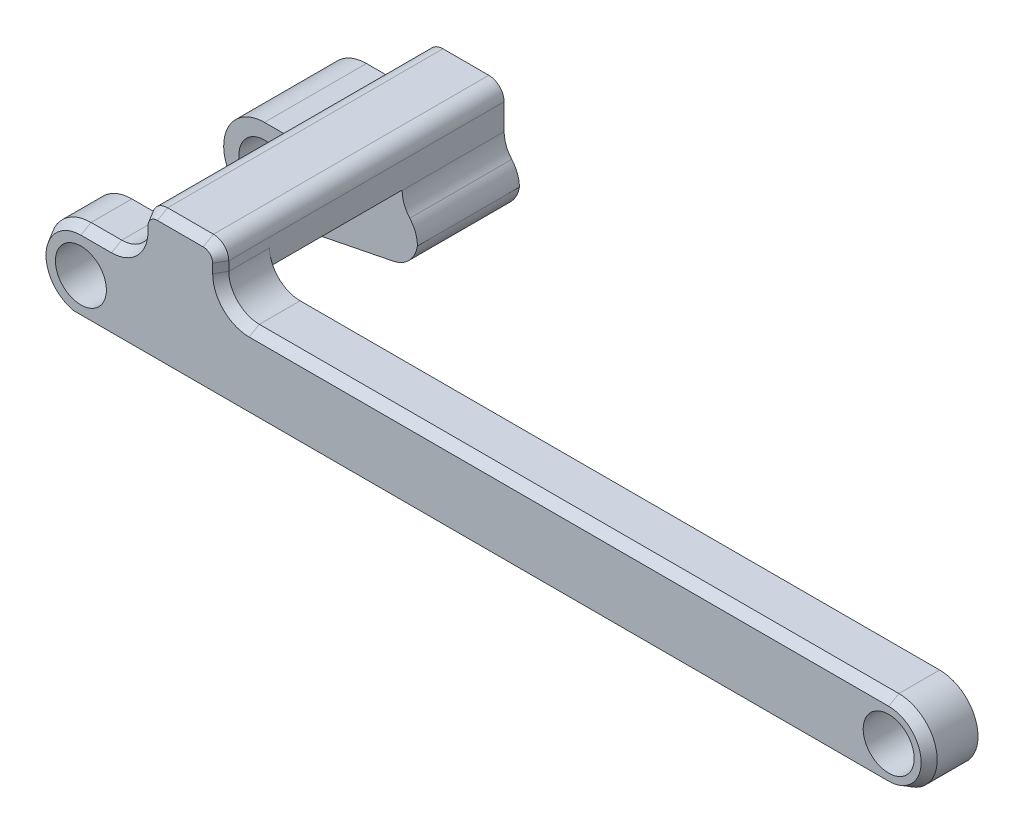
SolidWorks part; units mm, degrees
ref_plane "Front Plane" through (0, 0, 0) normal (0, 0, 1) x (1, 0, 0)
ref_plane "Top Plane" through (0, 0, 0) normal (0, 1, 0) x (1, 0, 0)
ref_plane "Right Plane" through (0, 0, 0) normal (1, 0, 0) x (0, 0, -1)
sketch "Sketch1" plane through (0, 0, 0) normal (0, 0, 1) x (1, 0, 0)
  line L0 (0, 0) -> (4.5, 0) construction
  line L1 (0, 4) -> (15, 4)
  line L2 (0, -4) -> (15, -4)
  line L3 (15, -4) -> (15, 4)
  circle A0 centre (0, 0) radius 2.5
  arc A1 (0, 4) -> (0, -4) centre (0, 0) ccw
extrude "Boss-Extrude1" add sketch "Sketch1" along normal blind 10
fillet "Fillet1" radius 3 2 edges at (15, -4, 5) (15, 4, 5)
sketch "Sketch2" plane through (0, 0, 10) normal (0, 0, 1) x (1, 0, 0)
  line L0 (15, -1) -> (0, -4)
  line L1 (0, -4) -> (12, -4) construction
  line L2 (0, -4) -> (15, -4)
  line L3 (15, -4) -> (15, -1)
  dimension "D1" = 15
extrude "Cut-Extrude1" cut sketch "Sketch2" against normal through all
fillet "Fillet2" radius 3 1 edges at (15, -1, 5)
fillet "Fillet3" radius 3 1 edges at (0, -4, 5)
sketch "Sketch3" plane through (0, 4, 0) normal (0, 1, 0) x (1, 0, 0)
  line L0 (12, 0) -> (0, 0) construction
  line L1 (6, 0) -> (13.5, 0)
  line L2 (6, 0) -> (6, -10)
  line L3 (6, -10) -> (13.5, -10)
  line L4 (13.5, 0) -> (13.5, -10)
  line L5 (12, -10) -> (15, -10) construction
extrude "Boss-Extrude2" add sketch "Sketch3" along normal blind 3 and the other way blind 2
sketch "Sketch4" plane through (0, 0, 10) normal (0, 0, 1) x (1, 0, 0)
  line L0 (13.5, 3.5981) -> (13.5, 7) construction
  line L2 (6, 7) -> (6, 9)
  line L3 (6, 9) -> (13.5, 9)
  line L4 (13.5, 7) -> (13.5, 9)
  line L6 (6, 7) -> (6, 5)
  line L7 (6, 5) -> (13.5, 5)
  line L8 (13.5, 7) -> (13.5, 5)
  dimension "D1" = 4
  dimension "D2" = 2
extrude "Boss-Extrude3" add sketch "Sketch4" along normal blind 13 and the other way up to surface other way up to face at (7.0417, 1.9342, 0)
sketch "Sketch5" plane through (0, 0, 23) normal (0, 0, 1) x (1, 0, 0)
  line L0 (13.5, 3.5981) -> (13.5, 5) construction
  line L2 (6, 4) -> (6, 5) construction
  line L3 (6, 4) -> (0, 4) construction
  line L4 (13.5, 3.5981) -> (13.5, 5)
  line L6 (6, 4) -> (6, 5)
  line L7 (6, 4) -> (0, 4)
  line L8 (-0.7921, -3.9208) -> (79.2079, -3.9208)
  line L9 (13.5, 3.5981) -> (79.2079, 3.5981)
  line L15 (6, 9) -> (6, 5)
  line L16 (6, 5) -> (13.5, 5)
  line L17 (13.5, 5) -> (13.5, 9)
  line L18 (13.5, 9) -> (6, 9)
  line L19 (6, 9) -> (6, 5)
  line L21 (13.5, 5) -> (13.5, 9)
  line L22 (13.5, 9) -> (6, 9)
  arc A0 (0, 4) -> (-0.7921, -3.9208) centre (0, 0) ccw construction
  arc A1 (0, 4) -> (-0.7921, -3.9208) centre (0, 0) ccw
  arc A2 (79.2079, 3.5981) -> (79.2079, -3.9208) centre (79.2079, -0.1614) cw
  dimension "D4" = 3.7594
  dimension "D1" = 80
  dimension "D2" = 0
extrude "Boss-Extrude4" add sketch "Sketch5" along normal blind 5
sketch "Sketch6" plane through (0, 0, 23) normal (0, 0, -1) x (-1, 0, 0)
  circle A0 centre (0, 0) radius 2.5 construction
  circle A1 centre (0, 0) radius 2.5
  circle A2 centre (-79.2079, -0.1614) radius 2.5
extrude "Cut-Extrude2" cut sketch "Sketch6" against normal through all
fillet "Fillet5" radius 3 3 edges at (13.5, 3.5981, 5) (13.5, 3.5981, 25.5) (6, 4, 5)
sketch "Sketch8" plane through (0, 0, 28) normal (0, 0, 1) x (1, 0, 0)
  point P0 (79.2079, -0.1614)
sketch "Sketch9" plane through (0, 0, 23) normal (0, 0, -1) x (-1, 0, 0)
  point P0 (-79.2079, -0.1614)
sketch3d "3DSketch1"
  line L0 (79.2079, -0.1614, 23) -> (79.2079, -0.1614, 28) construction
fillet "Fillet6" radius 1.5 2 edges at (6, 9, 14) (13.5, 9, 14)
chamfer "Chamfer1" distance 1 angle 30 12 edges at (-3.9801, 0.398, 28) (1.5, 4, 28) (5.1213, 4.8787, 28) (6, 7.25, 28) (6.4393, 8.5607, 28) (9.75, 9, 28) (13.0607, 8.5607, 28) (39.2079, -3.9208, 28) (13.5, 7.049, 28) (82.9673, -0.1614, 28) (14.3787, 4.4768, 28) (47.8539, 3.5981, 28)
